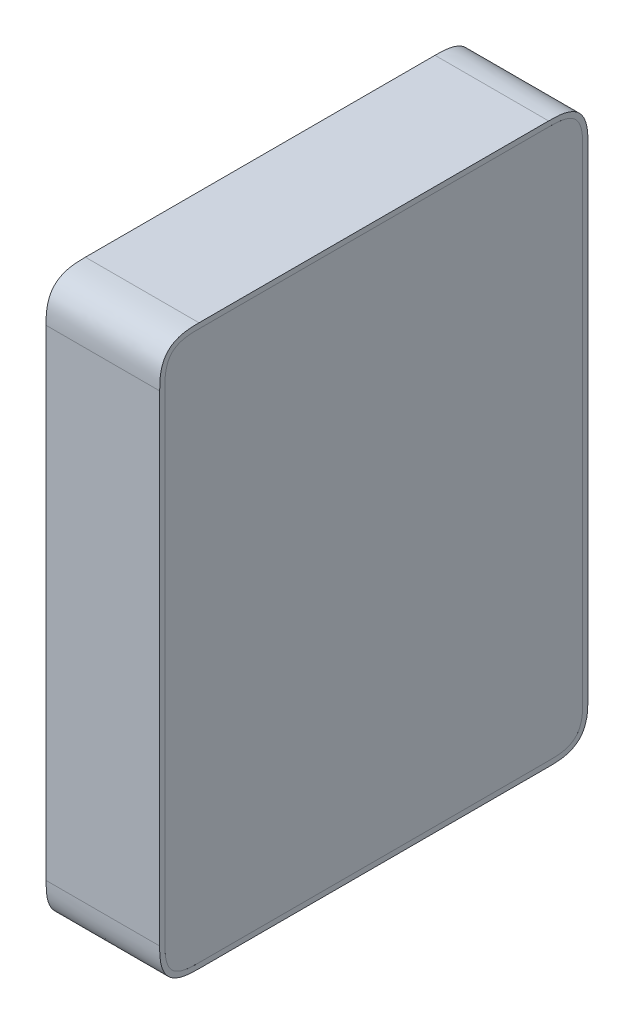
SolidWorks part; units mm, degrees
ref_plane "Front Plane" through (0, 0, 0) normal (0, 0, 1) x (1, 0, 0)
ref_plane "Top Plane" through (0, 0, 0) normal (0, 1, 0) x (1, 0, 0)
ref_plane "Right Plane" through (0, 0, 0) normal (1, 0, 0) x (0, 0, -1)
sketch "Sketch1" plane through (0, 0, 0) normal (1, 0, 0) x (0, 0, -1)
  line L1 (-245, 320) -> (245, 320)
  line L2 (-245, 320) -> (-245, -320)
  line L3 (-245, -320) -> (245, -320)
  line L4 (245, 320) -> (245, -320)
  line L5 (-245, 320) -> (245, -320) construction
  line L6 (-245, -320) -> (245, 320) construction
  point P0 (0, 0)
  dimension "D1" = 640
  dimension "D2" = 490
extrude "Boss-Extrude1" add sketch "Sketch1" along normal blind 130
fillet "Fillet2" radius 45 4 edges at (65, -320, -245) (65, 320, -245) (65, -320, 245) (65, 320, 245) curvature continuous yes
chamfer "Chamfer1" [suppressed] distance 40 angle 45
shell "Shell2" thickness 12 removed face at (130, 0, 0)
fillet "Fillet1" [suppressed] radius 20
sketch "Sketch4" plane through (130, 0, 0) normal (1, 0, 0) x (0, 0, -1)
  line L17 (200, 314) -> (-200, 314)
  line L19 (-239, 275) -> (-239, -275)
  line L21 (-200, -314) -> (200, -314)
  line L23 (239, -275) -> (239, 275)
  line L25 (200, 314) -> (-200, 314)
  line L27 (-239, 275) -> (-239, -275)
  line L29 (-200, -314) -> (200, -314)
  line L31 (239, -275) -> (239, 275)
  spline S4 degree 3 poles (173.6969, -2310.2609) (61.653, -229.2917) (138.9234, -317.5889) (209.5177, -313.7749) (210.8706, -313.6656) (213.5683, -313.3531) (214.9131, -313.1505) (217.5919, -312.6224) (218.9322, -312.2946) (221.5501, -311.4962) (222.8311, -311.0252) (224.6989, -310.1813) (225.3125, -309.8769) (226.5191, -309.2153) (227.1095, -308.859) (228.8155, -307.7211) (229.8745, -306.8659) (231.0865, -305.6589) (231.3233, -305.4106) (231.7856, -304.9001) (232.0114, -304.6376) (232.6646, -303.8388) (233.071, -303.2881) (234.2111, -301.5871) (234.8664, -300.3879) (235.7205, -298.509) (235.9823, -297.872) (236.4613, -296.5911) (236.6794, -295.9453) (237.2778, -293.9939) (237.6033, -292.6745) (238.1349, -290.0058) (238.341, -288.6565) (238.66, -285.9346) (238.7713, -284.5695) (242.6228, -213.9788) (153.9723, -141.1304) (2231.8089, -153.2058) knots -3.066098 -3.066098 -3.066098 -3.066098 0.125 0.125 0.1875 0.1875 0.25 0.25 0.3125 0.3125 0.375 0.375 0.40625 0.40625 0.4375 0.4375 0.5 0.5 0.515625 0.515625 0.53125 0.53125 0.5625 0.5625 0.625 0.625 0.65625 0.65625 0.6875 0.6875 0.75 0.75 0.8125 0.8125 0.875 0.875 4.043643 4.043643 4.043643 4.043643 only from (200, -314) to (239, -275)
  spline S5 degree 3 poles (200, -314) (202.7249, -314) (205.4494, -313.9947) (209.5177, -313.7749) (210.8706, -313.6656) (213.5683, -313.3531) (214.9131, -313.1505) (217.5919, -312.6224) (218.9322, -312.2946) (221.5501, -311.4962) (222.8311, -311.0252) (224.6989, -310.1813) (225.3125, -309.8769) (226.5191, -309.2153) (227.1095, -308.859) (228.8155, -307.7211) (229.8745, -306.8659) (231.0865, -305.6589) (231.3233, -305.4106) (231.7856, -304.9001) (232.0114, -304.6376) (232.6646, -303.8388) (233.071, -303.2881) (234.2111, -301.5871) (234.8664, -300.3879) (235.7205, -298.509) (235.9823, -297.872) (236.4613, -296.5911) (236.6794, -295.9453) (237.2778, -293.9939) (237.6033, -292.6745) (238.1349, -290.0058) (238.341, -288.6565) (238.66, -285.9346) (238.7713, -284.5695) (238.9948, -280.4732) (239, -277.7367) (239, -275) knots 0 0 0 0 0.125 0.125 0.1875 0.1875 0.25 0.25 0.3125 0.3125 0.375 0.375 0.40625 0.40625 0.4375 0.4375 0.5 0.5 0.515625 0.515625 0.53125 0.53125 0.5625 0.5625 0.625 0.625 0.65625 0.65625 0.6875 0.6875 0.75 0.75 0.8125 0.8125 0.875 0.875 1 1 1 1
  spline S6 degree 3 poles (2235.2609, 248.6969) (154.2917, 136.653) (242.5889, 213.9234) (238.7749, 284.5177) (238.6656, 285.8706) (238.3531, 288.5683) (238.1505, 289.9131) (237.6224, 292.5919) (237.2946, 293.9322) (236.4962, 296.5501) (236.0252, 297.8311) (235.1813, 299.6989) (234.8769, 300.3125) (234.2153, 301.5191) (233.859, 302.1095) (232.7211, 303.8155) (231.8659, 304.8745) (230.6589, 306.0865) (230.4106, 306.3233) (229.9001, 306.7856) (229.6376, 307.0114) (228.8388, 307.6646) (228.2881, 308.071) (226.5871, 309.2111) (225.3879, 309.8664) (223.509, 310.7205) (222.872, 310.9823) (221.5911, 311.4613) (220.9453, 311.6794) (218.9939, 312.2778) (217.6745, 312.6033) (215.0058, 313.1349) (213.6565, 313.341) (210.9346, 313.66) (209.5695, 313.7713) (138.9788, 317.6228) (66.1304, 228.9723) (78.2058, 2306.8089) knots -3.066098 -3.066098 -3.066098 -3.066098 0.125 0.125 0.1875 0.1875 0.25 0.25 0.3125 0.3125 0.375 0.375 0.40625 0.40625 0.4375 0.4375 0.5 0.5 0.515625 0.515625 0.53125 0.53125 0.5625 0.5625 0.625 0.625 0.65625 0.65625 0.6875 0.6875 0.75 0.75 0.8125 0.8125 0.875 0.875 4.043643 4.043643 4.043643 4.043643 only from (239, 275) to (200, 314)
  spline S7 degree 3 poles (239, 275) (239, 277.7249) (238.9947, 280.4494) (238.7749, 284.5177) (238.6656, 285.8706) (238.3531, 288.5683) (238.1505, 289.9131) (237.6224, 292.5919) (237.2946, 293.9322) (236.4962, 296.5501) (236.0252, 297.8311) (235.1813, 299.6989) (234.8769, 300.3125) (234.2153, 301.5191) (233.859, 302.1095) (232.7211, 303.8155) (231.8659, 304.8745) (230.6589, 306.0865) (230.4106, 306.3233) (229.9001, 306.7856) (229.6376, 307.0114) (228.8388, 307.6646) (228.2881, 308.071) (226.5871, 309.2111) (225.3879, 309.8664) (223.509, 310.7205) (222.872, 310.9823) (221.5911, 311.4613) (220.9453, 311.6794) (218.9939, 312.2778) (217.6745, 312.6033) (215.0058, 313.1349) (213.6565, 313.341) (210.9346, 313.66) (209.5695, 313.7713) (205.4732, 313.9948) (202.7367, 314) (200, 314) knots 0 0 0 0 0.125 0.125 0.1875 0.1875 0.25 0.25 0.3125 0.3125 0.375 0.375 0.40625 0.40625 0.4375 0.4375 0.5 0.5 0.515625 0.515625 0.53125 0.53125 0.5625 0.5625 0.625 0.625 0.65625 0.65625 0.6875 0.6875 0.75 0.75 0.8125 0.8125 0.875 0.875 1 1 1 1
  spline S8 degree 3 poles (-173.6969, 2310.2609) (-61.653, 229.2917) (-138.9234, 317.5889) (-209.5177, 313.7749) (-210.8706, 313.6656) (-213.5683, 313.3531) (-214.9131, 313.1505) (-217.5919, 312.6224) (-218.9322, 312.2946) (-221.5501, 311.4962) (-222.8311, 311.0252) (-224.6989, 310.1813) (-225.3125, 309.8769) (-226.5191, 309.2153) (-227.1095, 308.859) (-228.8155, 307.7211) (-229.8745, 306.8659) (-231.0865, 305.6589) (-231.3233, 305.4106) (-231.7856, 304.9001) (-232.0114, 304.6376) (-232.6646, 303.8388) (-233.071, 303.2881) (-234.2111, 301.5871) (-234.8664, 300.3879) (-235.7205, 298.509) (-235.9823, 297.872) (-236.4613, 296.5911) (-236.6794, 295.9453) (-237.2778, 293.9939) (-237.6033, 292.6745) (-238.1349, 290.0058) (-238.341, 288.6565) (-238.66, 285.9346) (-238.7713, 284.5695) (-242.6228, 213.9788) (-153.9723, 141.1304) (-2231.8089, 153.2058) knots -3.066098 -3.066098 -3.066098 -3.066098 0.125 0.125 0.1875 0.1875 0.25 0.25 0.3125 0.3125 0.375 0.375 0.40625 0.40625 0.4375 0.4375 0.5 0.5 0.515625 0.515625 0.53125 0.53125 0.5625 0.5625 0.625 0.625 0.65625 0.65625 0.6875 0.6875 0.75 0.75 0.8125 0.8125 0.875 0.875 4.043643 4.043643 4.043643 4.043643 only from (-200, 314) to (-239, 275)
  spline S9 degree 3 poles (-200, 314) (-202.7249, 314) (-205.4494, 313.9947) (-209.5177, 313.7749) (-210.8706, 313.6656) (-213.5683, 313.3531) (-214.9131, 313.1505) (-217.5919, 312.6224) (-218.9322, 312.2946) (-221.5501, 311.4962) (-222.8311, 311.0252) (-224.6989, 310.1813) (-225.3125, 309.8769) (-226.5191, 309.2153) (-227.1095, 308.859) (-228.8155, 307.7211) (-229.8745, 306.8659) (-231.0865, 305.6589) (-231.3233, 305.4106) (-231.7856, 304.9001) (-232.0114, 304.6376) (-232.6646, 303.8388) (-233.071, 303.2881) (-234.2111, 301.5871) (-234.8664, 300.3879) (-235.7205, 298.509) (-235.9823, 297.872) (-236.4613, 296.5911) (-236.6794, 295.9453) (-237.2778, 293.9939) (-237.6033, 292.6745) (-238.1349, 290.0058) (-238.341, 288.6565) (-238.66, 285.9346) (-238.7713, 284.5695) (-238.9948, 280.4732) (-239, 277.7367) (-239, 275) knots 0 0 0 0 0.125 0.125 0.1875 0.1875 0.25 0.25 0.3125 0.3125 0.375 0.375 0.40625 0.40625 0.4375 0.4375 0.5 0.5 0.515625 0.515625 0.53125 0.53125 0.5625 0.5625 0.625 0.625 0.65625 0.65625 0.6875 0.6875 0.75 0.75 0.8125 0.8125 0.875 0.875 1 1 1 1
  spline S10 degree 3 poles (-2235.2609, -248.6969) (-154.2917, -136.653) (-242.5889, -213.9234) (-238.7749, -284.5177) (-238.6656, -285.8706) (-238.3531, -288.5683) (-238.1505, -289.9131) (-237.6224, -292.5919) (-237.2946, -293.9322) (-236.4962, -296.5501) (-236.0252, -297.8311) (-235.1813, -299.6989) (-234.8769, -300.3125) (-234.2153, -301.5191) (-233.859, -302.1095) (-232.7211, -303.8155) (-231.8659, -304.8745) (-230.6589, -306.0865) (-230.4106, -306.3233) (-229.9001, -306.7856) (-229.6376, -307.0114) (-228.8388, -307.6646) (-228.2881, -308.071) (-226.5871, -309.2111) (-225.3879, -309.8664) (-223.509, -310.7205) (-222.872, -310.9823) (-221.5911, -311.4613) (-220.9453, -311.6794) (-218.9939, -312.2778) (-217.6745, -312.6033) (-215.0058, -313.1349) (-213.6565, -313.341) (-210.9346, -313.66) (-209.5695, -313.7713) (-138.9788, -317.6228) (-66.1304, -228.9723) (-78.2058, -2306.8089) knots -3.066098 -3.066098 -3.066098 -3.066098 0.125 0.125 0.1875 0.1875 0.25 0.25 0.3125 0.3125 0.375 0.375 0.40625 0.40625 0.4375 0.4375 0.5 0.5 0.515625 0.515625 0.53125 0.53125 0.5625 0.5625 0.625 0.625 0.65625 0.65625 0.6875 0.6875 0.75 0.75 0.8125 0.8125 0.875 0.875 4.043643 4.043643 4.043643 4.043643 only from (-239, -275) to (-200, -314)
  spline S11 degree 3 poles (-239, -275) (-239, -277.7249) (-238.9947, -280.4494) (-238.7749, -284.5177) (-238.6656, -285.8706) (-238.3531, -288.5683) (-238.1505, -289.9131) (-237.6224, -292.5919) (-237.2946, -293.9322) (-236.4962, -296.5501) (-236.0252, -297.8311) (-235.1813, -299.6989) (-234.8769, -300.3125) (-234.2153, -301.5191) (-233.859, -302.1095) (-232.7211, -303.8155) (-231.8659, -304.8745) (-230.6589, -306.0865) (-230.4106, -306.3233) (-229.9001, -306.7856) (-229.6376, -307.0114) (-228.8388, -307.6646) (-228.2881, -308.071) (-226.5871, -309.2111) (-225.3879, -309.8664) (-223.509, -310.7205) (-222.872, -310.9823) (-221.5911, -311.4613) (-220.9453, -311.6794) (-218.9939, -312.2778) (-217.6745, -312.6033) (-215.0058, -313.1349) (-213.6565, -313.341) (-210.9346, -313.66) (-209.5695, -313.7713) (-205.4732, -313.9948) (-202.7367, -314) (-200, -314) knots 0 0 0 0 0.125 0.125 0.1875 0.1875 0.25 0.25 0.3125 0.3125 0.375 0.375 0.40625 0.40625 0.4375 0.4375 0.5 0.5 0.515625 0.515625 0.53125 0.53125 0.5625 0.5625 0.625 0.625 0.65625 0.65625 0.6875 0.6875 0.75 0.75 0.8125 0.8125 0.875 0.875 1 1 1 1
  dimension "D1" = 6
extrude "Cut-Extrude1" cut sketch "Sketch4" against normal blind 4
extrude "Boss-Extrude2" add sketch "Sketch4<2>" against normal blind 4 separate body
sketch "Sketch4<2>" plane through (130, 0, 0) normal (1, 0, 0) x (0, 0, -1) same geometry as "Sketch4"
